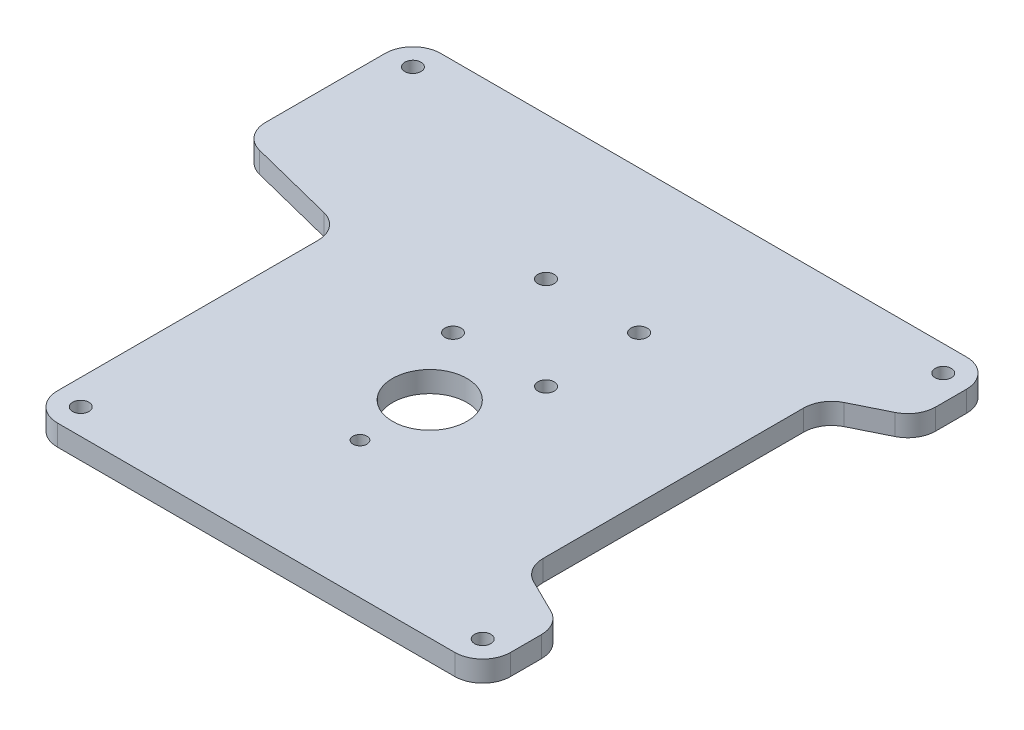
SolidWorks part; units mm, degrees
ref_plane "Front Plane" through (0, 0, 0) normal (0, 0, 1) x (1, 0, 0)
ref_plane "Top Plane" through (0, 0, 0) normal (0, 1, 0) x (1, 0, 0)
ref_plane "Right Plane" through (0, 0, 0) normal (1, 0, 0) x (0, 0, -1)
sketch "Sketch1" plane through (0, 0, 0) normal (0, 1, 0) x (1, 0, 0)
  line L0 (-41.7, 0) -> (41.7, 0) construction
  line L1 (-35.7, -55) -> (49.7, -55)
  line L2 (55.7, -49) -> (55.7, -42.3778)
  line L3 (52.3607, -37) -> (45.0393, -33.3778)
  line L4 (41.7, -28) -> (41.7, 28)
  line L5 (45.0393, 33.3778) -> (52.3607, 37)
  line L6 (55.7, 42.3778) -> (55.7, 49)
  line L7 (49.7, 55) -> (-63.3, 55)
  line L8 (-69.3, 49) -> (-69.3, 23.3173)
  line L9 (-64.7694, 17.5) -> (-46.2306, 12.8173)
  line L10 (-41.7, 7) -> (-41.7, -49)
  line L11 (-36.8, 20.5) -> (23.2, 20.5) construction
  line L12 (34.04, -3.15) -> (35.74, -3.15) construction
  line L13 (34.04, -3.15) -> (34.04, 3.15) construction
  line L14 (34.04, 3.15) -> (35.74, 3.15) construction
  line L15 (35.74, -3.15) -> (35.74, 3.15) construction
  line L16 (34.04, -3.15) -> (35.74, 3.15) construction
  line L17 (34.04, 3.15) -> (35.74, -3.15) construction
  line L18 (-33.5, -3.15) -> (-31.8, -3.15) construction
  line L19 (-33.5, -3.15) -> (-33.5, 3.15) construction
  line L20 (-33.5, 3.15) -> (-31.8, 3.15) construction
  line L21 (-31.8, -3.15) -> (-31.8, 3.15) construction
  line L22 (-33.5, -3.15) -> (-31.8, 3.15) construction
  line L23 (-33.5, 3.15) -> (-31.8, -3.15) construction
  line L24 (23.2, 20.5) -> (41.7, 20.5) construction
  line L25 (-41.7, -20) -> (-6.7, -20) construction
  line L26 (-6.7, -20) -> (-6.7, -55) construction
  line L27 (50.2, 55) -> (50.2, 49.5) construction
  line L28 (50.2, 49.5) -> (55.7, 49.5) construction
  line L29 (-63.8, 55) -> (-63.8, 49.5) construction
  line L30 (-63.8, 49.5) -> (-69.3, 49.5) construction
  line L31 (-41.7, -49.5) -> (-36.2, -49.5) construction
  line L32 (-36.2, -49.5) -> (-36.2, -55) construction
  line L33 (50.2, -55) -> (50.2, -49.5) construction
  line L34 (50.2, -49.5) -> (55.7, -49.5) construction
  line L35 (0, 14.3181) -> (0, 0) construction
  line L36 (-10, 4.3181) -> (10, 4.3181) construction
  line L37 (-10, 4.3181) -> (-10, 24.3181) construction
  line L38 (-10, 24.3181) -> (10, 24.3181) construction
  line L39 (10, 4.3181) -> (10, 24.3181) construction
  line L40 (-10, 4.3181) -> (10, 24.3181) construction
  line L41 (-10, 24.3181) -> (10, 4.3181) construction
  line L42 (0, 0) -> (0, -25.6819) construction
  line L43 (10, 4.3181) -> (10, -25.6819) construction
  line L44 (10, -25.6819) -> (-10, -25.6819) construction
  line L45 (-10, -25.6819) -> (-10, 4.3181) construction
  line L46 (10, -10.6819) -> (-10, -10.6819) construction
  arc A0 (49.7, -55) -> (55.7, -49) centre (49.7, -49) ccw
  arc A1 (55.7, -42.3778) -> (52.3607, -37) centre (49.7, -42.3778) ccw
  arc A2 (45.0393, -33.3778) -> (41.7, -28) centre (47.7, -28) cw
  arc A3 (41.7, 28) -> (45.0393, 33.3778) centre (47.7, 28) cw
  arc A4 (52.3607, 37) -> (55.7, 42.3778) centre (49.7, 42.3778) ccw
  arc A5 (55.7, 49) -> (49.7, 55) centre (49.7, 49) ccw
  arc A6 (-63.3, 55) -> (-69.3, 49) centre (-63.3, 49) ccw
  arc A7 (-69.3, 23.3173) -> (-64.7694, 17.5) centre (-63.3, 23.3173) ccw
  arc A8 (-46.2306, 12.8173) -> (-41.7, 7) centre (-47.7, 7) cw
  arc A9 (-41.7, -49) -> (-35.7, -55) centre (-35.7, -49) ccw
  circle A10 centre (-63.8, 49.5) radius 1.75
  circle A11 centre (50.2, 49.5) radius 1.5 construction
  circle A12 centre (-36.2, -49.5) radius 1.75
  circle A13 centre (50.2, -49.5) radius 1.75
  circle A14 centre (-36.8, 20.5) radius 2.75 construction
  circle A15 centre (23.2, 20.5) radius 2.5 construction
  circle A16 centre (-6.7, -20) radius 2.75 construction
  circle A17 centre (23.2, 20.5) radius 2.75 construction
  circle A18 centre (50.2, 49.5) radius 1.75
  circle A19 centre (10, 24.3181) radius 1.5 construction
  circle A20 centre (-10, 24.3181) radius 1.75
  circle A21 centre (-10, 4.3181) radius 1.75
  circle A22 centre (10, 4.3181) radius 1.75
  circle A23 centre (10, 24.3181) radius 1.75
  circle A24 centre (0, -25.6819) radius 1.25 construction
  circle A25 centre (0, -25.6819) radius 1.5
  circle A26 centre (0, -10.6819) radius 8
  point P2 (0, 0)
  point P37 (41.7, 0)
  point P49 (34.89, 0)
  point P54 (-32.65, 0)
  point P74 (0, 0)
  dimension "D4" = 6
  dimension "D15" = 5
  dimension "D21" = 3
  dimension "D24" = 3
  dimension "D28" = 2.5
  dimension "D30" = 16
  dimension "D1" = 110
  dimension "D2" = 125
  dimension "D3" = 18
  dimension "D5" = 27
  dimension "D6" = 83.4
  dimension "D7" = 27.6
  dimension "D8" = 37.5
  dimension "D9" = 48
  dimension "D10" = 6.3
  dimension "D11" = 1.7
  dimension "D12" = 8.2
  dimension "D13" = 65.84
  dimension "D16" = 18.5
  dimension "D17" = 60
  dimension "D18" = 34.5
  dimension "D19" = 35
  dimension "D22" = 5.5
  dimension "D25" = 20
  dimension "D26" = 40
  dimension "D29" = 4.3181
  dimension "D14" = 0.25
  dimension "D20" = 0.25
  dimension "D23" = 0.25
  dimension "D27" = 0.25
extrude "Boss-Extrude1" add sketch "Sketch1" along normal blind 4.5
equation "\"Tolerance\"=0.25"
equation "\"D14@Sketch1\"=\"Tolerance\""
equation "\"D20@Sketch1\"=\"Tolerance\""
equation "\"D23@Sketch1\"=\"Tolerance\""
equation "\"D27@Sketch1\"=\"Tolerance\""
